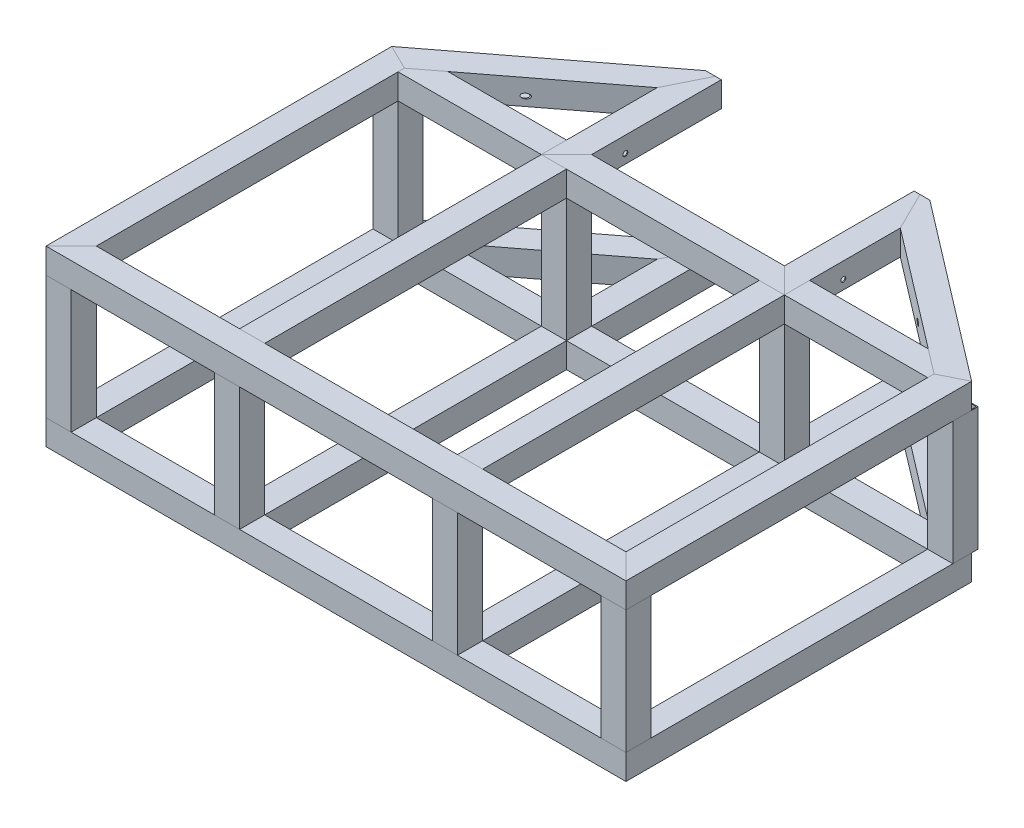
SolidWorks part; units mm, degrees
material "AISI 1020"
ref_plane "Front Plane" through (0, 0, 0) normal (0, 0, 1) x (1, 0, 0)
ref_plane "Top Plane" through (0, 0, 0) normal (0, 1, 0) x (1, 0, 0)
ref_plane "Right Plane" through (0, 0, 0) normal (1, 0, 0) x (0, 0, -1)
sketch "Sketch1" plane through (0, 0, 0) normal (0, 1, 0) x (1, 0, 0)
  line L1 (-110, 159.3494) -> (-280, 29.3494)
  line L2 (-280, 29.3494) -> (-280, -300.6506)
  line L3 (-280, -300.6506) -> (280, -300.6506)
  line L4 (280, -300.6506) -> (280, 29.3494)
  line L5 (280, 29.3494) -> (110, 159.3494)
  dimension "D1" = 220
  dimension "D2" = 560
  dimension "D3" = 110
  dimension "D4" = 460
  dimension "D5" = 330
other "Al tube square AL TUBE 1 SQR X 0.035 WALL(1)"
ref_plane "Plane1" through (-110, 0, -159.3494) normal (-0.7944, 0, 0.6075) x (0.6075, 0, 0.7944)
sketch "Sketch132" plane through (-110, 0, -159.3494) normal (-0.7944, 0, 0.6075) x (0.6075, 0, 0.7944)
  line L0 (-11.811, -11.811) -> (-11.811, 11.811)
  line L1 (11.811, 11.811) -> (-11.811, 11.811)
  line L2 (11.811, 11.811) -> (11.811, -11.811)
  line L3 (-11.811, -11.811) -> (11.811, -11.811)
  line L4 (-12.7, -12.7) -> (12.7, -12.7)
  line L5 (-12.7, -12.7) -> (-12.7, 12.7)
  line L6 (12.7, 12.7) -> (-12.7, 12.7)
  line L7 (12.7, 12.7) -> (12.7, -12.7)
  line L8 (0, -11.811) -> (0, -12.7) construction
  line L9 (0, -11.811) -> (0, 11.811) construction
  line L10 (0, 11.811) -> (0, 12.7) construction
  line L11 (12.7, 0) -> (11.811, 0) construction
  line L12 (11.811, 0) -> (-11.811, 0) construction
  line L13 (-11.811, 0) -> (-12.7, 0) construction
  point P14 (0, 0)
  point P17 (0, 0)
  dimension "Thickness" = 0.889
  dimension "V_leg" = 25.4
  dimension "H_leg" = 25.4
sketch "Sketch12" plane through (0, 0, 0) normal (0, 1, 0) x (1, 0, 0)
  line L0 (-110, 159.3494) -> (-110, 29.3494)
  line L1 (-110, 29.3494) -> (110, 29.3494)
  line L2 (110, 159.3494) -> (110, 29.3494)
  line L3 (-267.3, 29.3494) -> (-292.7, 29.3494) construction
  point P8 (-280, 29.3494)
other "Al tube square AL TUBE 1 SQR X 0.035 WALL(2)"
ref_plane "Plane2" through (-110, 0, -159.3494) normal (0, 0, 1) x (1, 0, 0)
sketch "Sketch134" plane through (-110, 0, -159.3494) normal (0, 0, 1) x (1, 0, 0)
  line L0 (-11.811, -11.811) -> (-11.811, 11.811)
  line L1 (11.811, 11.811) -> (-11.811, 11.811)
  line L2 (11.811, 11.811) -> (11.811, -11.811)
  line L3 (-11.811, -11.811) -> (11.811, -11.811)
  line L4 (-12.7, -12.7) -> (12.7, -12.7)
  line L5 (-12.7, -12.7) -> (-12.7, 12.7)
  line L6 (12.7, 12.7) -> (-12.7, 12.7)
  line L7 (12.7, 12.7) -> (12.7, -12.7)
  line L8 (0, -11.811) -> (0, -12.7) construction
  line L9 (0, -11.811) -> (0, 11.811) construction
  line L10 (0, 11.811) -> (0, 12.7) construction
  line L11 (12.7, 0) -> (11.811, 0) construction
  line L12 (11.811, 0) -> (-11.811, 0) construction
  line L13 (-11.811, 0) -> (-12.7, 0) construction
  point P14 (0, 0)
  point P17 (0, 0)
  dimension "Thickness" = 0.889
  dimension "V_leg" = 25.4
  dimension "H_leg" = 25.4
ref_plane "Plane3" through (0, 150, 0) normal (0, 1, 0) x (1, 0, 0)
sketch "Sketch14" plane through (0, 150, 0) normal (0, 1, 0) x (1, 0, 0)
  line L0 (-110, 159.3494) -> (-280, 29.3494)
  line L1 (-280, 29.3494) -> (-280, -300.6506)
  line L2 (-280, -300.6506) -> (280, -300.6506)
  line L3 (280, -300.6506) -> (280, 29.3494)
  line L4 (280, 29.3494) -> (110, 159.3494)
  line L5 (110, 159.3494) -> (110, 29.3494)
  line L6 (110, 29.3494) -> (-110, 29.3494)
  line L7 (-110, 29.3494) -> (-110, 159.3494)
other "Al tube square AL TUBE 1 SQR X 0.035 WALL(3)"
ref_plane "Plane4" through (-280, 150, -29.3494) normal (0, 0, 1) x (1, 0, 0)
sketch "Sketch136" plane through (-280, 150, -29.3494) normal (0, 0, 1) x (1, 0, 0)
  line L0 (-11.811, -11.811) -> (-11.811, 11.811)
  line L1 (11.811, 11.811) -> (-11.811, 11.811)
  line L2 (11.811, 11.811) -> (11.811, -11.811)
  line L3 (-11.811, -11.811) -> (11.811, -11.811)
  line L4 (-12.7, -12.7) -> (12.7, -12.7)
  line L5 (-12.7, -12.7) -> (-12.7, 12.7)
  line L6 (12.7, 12.7) -> (-12.7, 12.7)
  line L7 (12.7, 12.7) -> (12.7, -12.7)
  line L8 (0, -11.811) -> (0, -12.7) construction
  line L9 (0, -11.811) -> (0, 11.811) construction
  line L10 (0, 11.811) -> (0, 12.7) construction
  line L11 (12.7, 0) -> (11.811, 0) construction
  line L12 (11.811, 0) -> (-11.811, 0) construction
  line L13 (-11.811, 0) -> (-12.7, 0) construction
  point P14 (0, 0)
  point P17 (0, 0)
  dimension "Thickness" = 0.889
  dimension "V_leg" = 25.4
  dimension "H_leg" = 25.4
other "Trim/Extend26"
other "Trim/Extend27"
other "Trim/Extend28"
other "Trim/Extend29"
other "Trim/Extend30"
other "Trim/Extend31"
other "Trim/Extend32"
other "Trim/Extend33"
other "Trim/Extend34"
other "Trim/Extend35"
other "Trim/Extend36"
other "Trim/Extend37"
other "Trim/Extend38"
other "Trim/Extend39"
other "Trim/Extend40"
other "Trim/Extend41"
sketch3d "3DSketch3"
  line L2 (110, 150, -29.3494) -> (110, 0, -29.3494)
  line L3 (-110, 150, -29.3494) -> (-110, 0, -29.3494)
  line L4 (-280, 150, -29.3494) -> (-280, 0, -29.3494)
  line L5 (-280, 150, 300.6506) -> (-280, 0, 300.6506)
  line L6 (280, 150, 300.6506) -> (280, 0, 300.6506)
  line L7 (280, 150, -29.3494) -> (280, 0, -29.3494)
other "Al tube square AL TUBE 1 SQR X 0.035 WALL(4)"
ref_plane "Plane7" through (-110, 150, -29.3494) normal (0, -1, 0) x (1, 0, 0)
sketch "Sketch138" plane through (-110, 150, -29.3494) normal (0, -1, 0) x (1, 0, 0)
  line L0 (-11.811, -11.811) -> (-11.811, 11.811)
  line L1 (11.811, 11.811) -> (-11.811, 11.811)
  line L2 (11.811, 11.811) -> (11.811, -11.811)
  line L3 (-11.811, -11.811) -> (11.811, -11.811)
  line L4 (-12.7, -12.7) -> (12.7, -12.7)
  line L5 (-12.7, -12.7) -> (-12.7, 12.7)
  line L6 (12.7, 12.7) -> (-12.7, 12.7)
  line L7 (12.7, 12.7) -> (12.7, -12.7)
  line L8 (0, -11.811) -> (0, -12.7) construction
  line L9 (0, -11.811) -> (0, 11.811) construction
  line L10 (0, 11.811) -> (0, 12.7) construction
  line L11 (12.7, 0) -> (11.811, 0) construction
  line L12 (11.811, 0) -> (-11.811, 0) construction
  line L13 (-11.811, 0) -> (-12.7, 0) construction
  point P14 (0, 0)
  point P17 (0, 0)
  dimension "Thickness" = 0.889
  dimension "V_leg" = 25.4
  dimension "H_leg" = 25.4
other "Trim/Extend44"
other "Trim/Extend45"
other "Trim/Extend46"
other "Trim/Extend47"
other "Trim/Extend49"
other "Trim/Extend50"
sketch "Sketch121" plane through (0, 150, 0) normal (0, 1, 0) x (1, 0, 0)
  line L0 (-110, 29.3494) -> (-110, -300.6506)
  line L1 (-280, -300.6506) -> (280, -300.6506) construction
  line L2 (110, 29.3494) -> (110, -300.6506)
sketch "Sketch122" plane through (0, 0, 0) normal (0, 1, 0) x (1, 0, 0)
  line L0 (-110, 29.3494) -> (-110, -300.6506)
  line L1 (110, 29.3494) -> (110, -300.6506)
other "Al tube square AL TUBE 1 SQR X 0.035 WALL(5)"
ref_plane "Plane8" through (-110, 0, -29.3494) normal (0, 0, 1) x (1, 0, 0)
sketch "Sketch140" plane through (-110, 0, -29.3494) normal (0, 0, 1) x (1, 0, 0)
  line L0 (-11.811, -11.811) -> (-11.811, 11.811)
  line L1 (11.811, 11.811) -> (-11.811, 11.811)
  line L2 (11.811, 11.811) -> (11.811, -11.811)
  line L3 (-11.811, -11.811) -> (11.811, -11.811)
  line L4 (-12.7, -12.7) -> (12.7, -12.7)
  line L5 (-12.7, -12.7) -> (-12.7, 12.7)
  line L6 (12.7, 12.7) -> (-12.7, 12.7)
  line L7 (12.7, 12.7) -> (12.7, -12.7)
  line L8 (0, -11.811) -> (0, -12.7) construction
  line L9 (0, -11.811) -> (0, 11.811) construction
  line L10 (0, 11.811) -> (0, 12.7) construction
  line L11 (12.7, 0) -> (11.811, 0) construction
  line L12 (11.811, 0) -> (-11.811, 0) construction
  line L13 (-11.811, 0) -> (-12.7, 0) construction
  point P14 (0, 0)
  point P17 (0, 0)
  dimension "Thickness" = 0.889
  dimension "V_leg" = 25.4
  dimension "H_leg" = 25.4
other "Trim/Extend51"
other "Trim/Extend52"
other "Trim/Extend53"
sketch3d "3DSketch5"
  line L0 (-110, 150, 300.6506) -> (-110, 0, 300.6506)
  line L1 (110, 150, 300.6506) -> (110, 0, 300.6506)
other "Al tube square AL TUBE 1 SQR X 0.035 WALL(6)"
ref_plane "Plane9" through (-110, 150, 300.6506) normal (0, -1, 0) x (1, 0, 0)
sketch "Sketch142" plane through (-110, 150, 300.6506) normal (0, -1, 0) x (1, 0, 0)
  line L0 (-11.811, -11.811) -> (-11.811, 11.811)
  line L1 (11.811, 11.811) -> (-11.811, 11.811)
  line L2 (11.811, 11.811) -> (11.811, -11.811)
  line L3 (-11.811, -11.811) -> (11.811, -11.811)
  line L4 (-12.7, -12.7) -> (12.7, -12.7)
  line L5 (-12.7, -12.7) -> (-12.7, 12.7)
  line L6 (12.7, 12.7) -> (-12.7, 12.7)
  line L7 (12.7, 12.7) -> (12.7, -12.7)
  line L8 (0, -11.811) -> (0, -12.7) construction
  line L9 (0, -11.811) -> (0, 11.811) construction
  line L10 (0, 11.811) -> (0, 12.7) construction
  line L11 (12.7, 0) -> (11.811, 0) construction
  line L12 (11.811, 0) -> (-11.811, 0) construction
  line L13 (-11.811, 0) -> (-12.7, 0) construction
  point P14 (0, 0)
  point P17 (0, 0)
  dimension "Thickness" = 0.889
  dimension "V_leg" = 25.4
  dimension "H_leg" = 25.4
other "Trim/Extend54"
sketch "Sketch126" plane through (0, 150, 0) normal (0, 1, 0) x (1, 0, 0)
  line L0 (-280, 29.3494) -> (-110, 29.3494)
  line L1 (110, 29.3494) -> (280, 29.3494)
other "Al tube square AL TUBE 1 SQR X 0.035 WALL(7)"
ref_plane "Plane10" through (-280, 150, -29.3494) normal (1, 0, 0) x (0, 0, -1)
sketch "Sketch144" plane through (-280, 150, -29.3494) normal (1, 0, 0) x (0, 0, -1)
  line L0 (-11.811, -11.811) -> (-11.811, 11.811)
  line L1 (11.811, 11.811) -> (-11.811, 11.811)
  line L2 (11.811, 11.811) -> (11.811, -11.811)
  line L3 (-11.811, -11.811) -> (11.811, -11.811)
  line L4 (-12.7, -12.7) -> (12.7, -12.7)
  line L5 (-12.7, -12.7) -> (-12.7, 12.7)
  line L6 (12.7, 12.7) -> (-12.7, 12.7)
  line L7 (12.7, 12.7) -> (12.7, -12.7)
  line L8 (0, -11.811) -> (0, -12.7) construction
  line L9 (0, -11.811) -> (0, 11.811) construction
  line L10 (0, 11.811) -> (0, 12.7) construction
  line L11 (12.7, 0) -> (11.811, 0) construction
  line L12 (11.811, 0) -> (-11.811, 0) construction
  line L13 (-11.811, 0) -> (-12.7, 0) construction
  point P14 (0, 0)
  point P17 (0, 0)
  dimension "Thickness" = 0.889
  dimension "V_leg" = 25.4
  dimension "H_leg" = 25.4
other "Trim/Extend55"
other "Trim/Extend56"
other "Trim/Extend57"
sketch3d "3DSketch6"
  line L0 (-280, 0, -29.3494) -> (-110, 0, -29.3494)
  line L1 (110, 0, -29.3494) -> (280, 0, -29.3494)
other "Al tube square AL TUBE 1 SQR X 0.035 WALL(8)"
ref_plane "Plane12" through (-280, 0, -29.3494) normal (1, 0, 0) x (0, 0, -1)
sketch "Sketch146" plane through (-280, 0, -29.3494) normal (1, 0, 0) x (0, 0, -1)
  line L0 (-11.811, -11.811) -> (-11.811, 11.811)
  line L1 (11.811, 11.811) -> (-11.811, 11.811)
  line L2 (11.811, 11.811) -> (11.811, -11.811)
  line L3 (-11.811, -11.811) -> (11.811, -11.811)
  line L4 (-12.7, -12.7) -> (12.7, -12.7)
  line L5 (-12.7, -12.7) -> (-12.7, 12.7)
  line L6 (12.7, 12.7) -> (-12.7, 12.7)
  line L7 (12.7, 12.7) -> (12.7, -12.7)
  line L8 (0, -11.811) -> (0, -12.7) construction
  line L9 (0, -11.811) -> (0, 11.811) construction
  line L10 (0, 11.811) -> (0, 12.7) construction
  line L11 (12.7, 0) -> (11.811, 0) construction
  line L12 (11.811, 0) -> (-11.811, 0) construction
  line L13 (-11.811, 0) -> (-12.7, 0) construction
  point P14 (0, 0)
  point P17 (0, 0)
  dimension "Thickness" = 0.889
  dimension "V_leg" = 25.4
  dimension "H_leg" = 25.4
other "Trim/Extend58"
other "Trim/Extend59"
sketch "Sketch147" plane through (0, 162.7, 0) normal (0, 1, 0) x (1, 0, 0)
  line L1 (-166.8458, 255.0324) -> (156.8308, 255.0324)
  line L2 (-166.8458, 255.0324) -> (-166.8458, 172.9055)
  line L3 (-166.8458, 172.9055) -> (156.8308, 172.9055)
  line L4 (156.8308, 255.0324) -> (156.8308, 172.9055)
extrude "Cut-Extrude1" cut sketch "Sketch147" against normal through all both
sketch "Sketch149" plane through (97.3, 0, 0) normal (-1, 0, 0) x (0, 0, 1)
  circle A0 centre (-76.1201, 146.5) radius 2.5
  dimension "D1" = 5
extrude "Cut-Extrude2" cut sketch "Sketch149" against normal through all both and the other way through all
